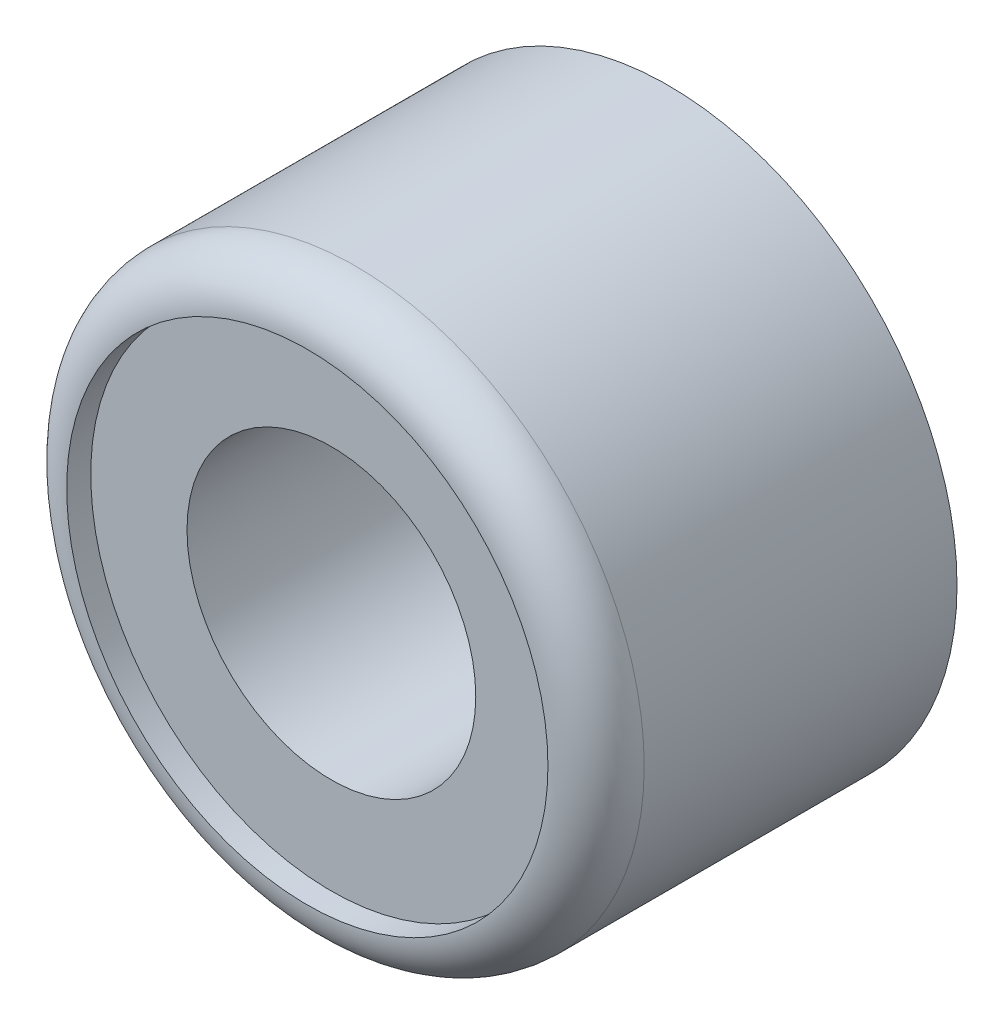
SolidWorks part; units mm, degrees
ref_plane "Front Plane" through (0, 0, 0) normal (0, 0, 1) x (1, 0, 0)
ref_plane "Top Plane" through (0, 0, 0) normal (0, 1, 0) x (1, 0, 0)
ref_plane "Right Plane" through (0, 0, 0) normal (1, 0, 0) x (0, 0, -1)
sketch "Sketch1" plane through (0, 0, 0) normal (0, 0, 1) x (1, 0, 0)
  circle A0 centre (0, 0) radius 3
  circle A1 centre (0, 0) radius 5
  circle A2 centre (0, 0) radius 6
  circle A3 centre (0, 0) radius 1.55
  dimension "D1" = 10
  dimension "D2" = 6
  dimension "D3" = 1
  dimension "D4" = 3.1
extrude "Boss-Extrude1" add sketch "Sketch1" along normal blind 1.5 contours A0 A3 | A0 | A3 region at (-2.9151, 0, 0)
extrude "Boss-Extrude3" add sketch "Sketch1<7>" along normal blind 7 contours A1 A0 region at (-4.8586, 0, 0)
sketch "Sketch1<7>" plane through (0, 0, 0) normal (0, 0, 1) x (1, 0, 0) same geometry as "Sketch1"
extrude "Boss-Extrude4" add sketch "Sketch1<9>" along normal blind 7.5 contours A2 A1 region at (-5.8303, 0, 0)
sketch "Sketch1<9>" plane through (0, 0, 0) normal (0, 0, 1) x (1, 0, 0) same geometry as "Sketch1"
fillet "Fillet1" radius 1 1 edges at (6, 0, 7.5)
